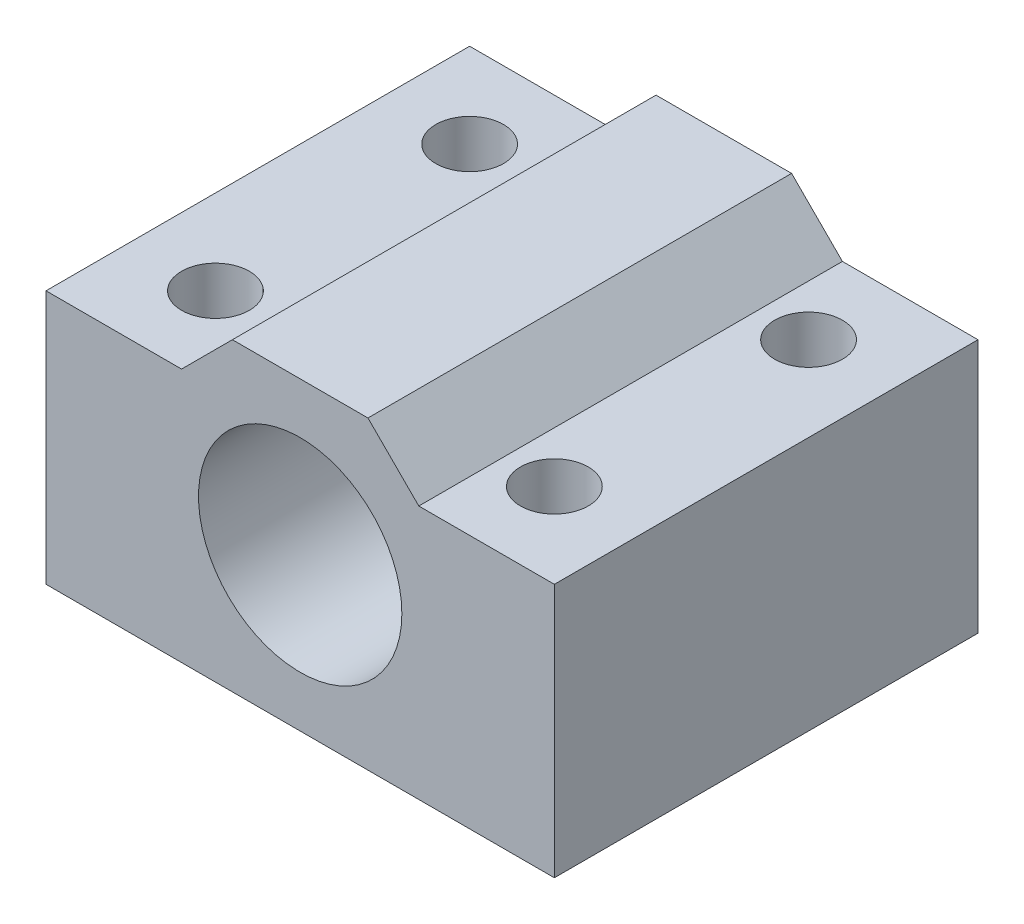
SolidWorks part; units mm, degrees
ref_plane "Plan de face" through (0, 0, 0) normal (0, 0, 1) x (1, 0, 0)
ref_plane "Plan de dessus" through (0, 0, 0) normal (0, 1, 0) x (1, 0, 0)
ref_plane "Plan de droite" through (0, 0, 0) normal (1, 0, 0) x (0, 0, -1)
sketch "Esquisse1" plane through (0, 0, 0) normal (0, 0, 1) x (1, 0, 0)
  line L0 (0, 0) -> (0, 18) construction
  line L1 (15, 0) -> (-15, 0)
  line L2 (-15, 0) -> (-15, 15)
  line L3 (-15, 15) -> (-7, 15)
  line L4 (-7, 15) -> (-4, 18)
  line L5 (-4, 18) -> (4, 18)
  line L6 (7, 15) -> (4, 18)
  line L7 (15, 15) -> (7, 15)
  line L8 (15, 0) -> (15, 15)
  dimension "D1" = 15
  dimension "D2" = 15
  dimension "D3" = 3
  dimension "D4" = 135
  dimension "D5" = 8
extrude "Boss.-Extru.1" add sketch "Esquisse1" along normal blind 25
sketch "Esquisse2" plane through (0, 0, 25) normal (0, 0, 1) x (1, 0, 0)
  line L0 (0, 0) -> (0, 9) construction
  circle A0 centre (0, 9) radius 6
  dimension "D1" = 12
  dimension "D2" = 9
extrude "Enlèv. mat.-Extru.1" cut sketch "Esquisse2" against normal up to vertex (25 mm away) up to point (15, 15, 0)
sketch "Esquisse3" plane through (0, 15, 0) normal (0, 1, 0) x (1, 0, 0)
  line L0 (0, 0) -> (0, -25) construction
  line L1 (4, -25) -> (-4, -25) construction
  line L2 (-15, -12.5) -> (15, -12.5) construction
  line L3 (-15, -25) -> (-15, 0) construction
  line L4 (15, -25) -> (15, 0) construction
  circle A0 centre (-10, -5) radius 2
  circle A1 centre (10, -5) radius 2
  circle A2 centre (10, -20) radius 2
  circle A3 centre (-10, -20) radius 2
  dimension "D1" = 4
  dimension "D2" = 20
  dimension "D3" = 15
extrude "Enlèv. mat.-Extru.2" cut sketch "Esquisse3" against normal through all
